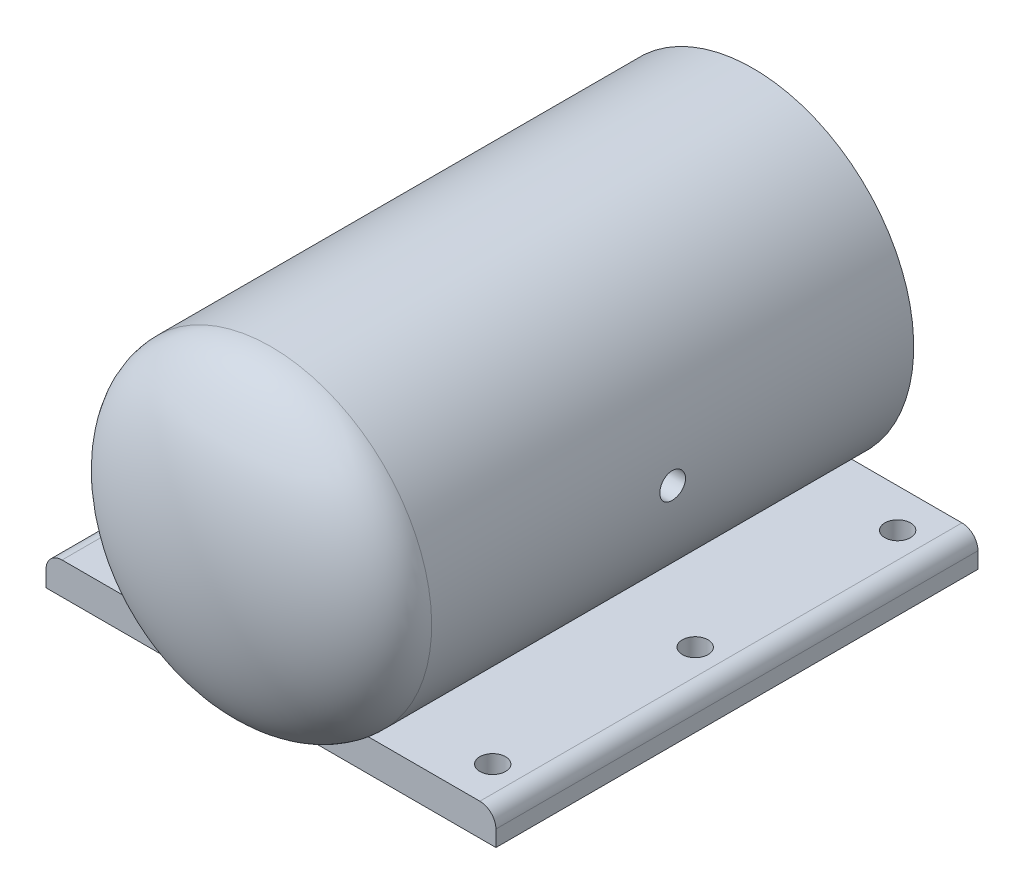
SolidWorks part; units mm, degrees
ref_plane "Front Plane" through (0, 0, 0) normal (0, 0, 1) x (1, 0, 0)
ref_plane "Top Plane" through (0, 0, 0) normal (0, 1, 0) x (1, 0, 0)
ref_plane "Right Plane" through (0, 0, 0) normal (1, 0, 0) x (0, 0, -1)
sketch "Sketch1" plane through (0, 0, 0) normal (0, 0, 1) x (1, 0, 0)
  line L0 (-32.5, -20) -> (-15, -20)
  line L1 (15, -20) -> (32.5, -20)
  line L2 (35, -22.5) -> (35, -25)
  line L3 (35, -25) -> (-35, -25)
  line L4 (-35, -25) -> (-35, -22.5)
  circle A0 centre (0, 0) radius 20
  arc A1 (15, -20) -> (-15, -20) centre (0, 0) ccw
  arc A2 (-35, -22.5) -> (-32.5, -20) centre (-32.5, -22.5) cw
  arc A3 (35, -22.5) -> (32.5, -20) centre (32.5, -22.5) ccw
  point P11 (0, -25)
  point P13 (-35, -20)
  dimension "D1" = 40
  dimension "D2" = 50
  dimension "D6" = 2.5
  dimension "D7" = 2.5
  dimension "D3" = 70
  dimension "D4" = 5
  dimension "D5" = 25
extrude "Boss-Extrude1" add sketch "Sketch1" along normal blind 75
sketch "Sketch2" plane through (0, -20, 0) normal (0, 1, 0) x (1, 0, 0)
  line L0 (-15, 0) -> (-32.5, 0) construction
  line L1 (-32.5, -75) -> (-32.5, 0) construction
  line L2 (-32.5, -37.5) -> (32.5, -37.5) construction
  line L3 (32.5, -75) -> (32.5, 0) construction
  line L4 (0, 0) -> (0, -75) construction
  line L5 (-25, -75) -> (25, -75) construction
  line L6 (28.5, -69) -> (28.5, -6) construction
  line L7 (-28.5, -69) -> (-28.5, -6) construction
  line L8 (-32.5, 0) -> (-35, 0) construction
  circle A0 centre (-28.5, -6) radius 2
  circle A1 centre (-28.5, -6) radius 2
  circle A2 centre (28.5, -6) radius 2
  circle A3 centre (28.5, -69) radius 2
  circle A4 centre (-28.5, -69) radius 2
  circle A5 centre (28.5, -37.5) radius 2
  circle A6 centre (-28.5, -37.5) radius 2
  point P26 (0, 0)
  point P27 (0, 0)
  dimension "D1" = 4
  dimension "D2" = 6
  dimension "D3" = 4
sketch "Sketch3" plane through (0, 0, 0) normal (1, 0, 0) x (0, 0, -1)
  line L0 (-75, -22.5) -> (0, -22.5) construction
  circle A0 centre (-37.5, 0) radius 2
  point P7 (-37.5, -22.5)
  dimension "D1" = 4
extrude "Cut-Extrude2" cut sketch "Sketch3" against normal through all both and the other way through all
sketch "Sketch4" plane through (0, 0, 0) normal (1, 0, 0) x (0, 0, -1)
  line L0 (0, 0) -> (-75, 0) construction
  line L3 (-75, 20) -> (-75, -20) construction
  line L4 (-87.5, 0) -> (-75, 0) construction
  line L5 (-87.5, 0) -> (-84.5, 0)
  line L6 (-75, 25) -> (-75, 22)
  ellipse E0 centre (-75, 0) end of major axis (-75, 25) minor radius 12.5 (-75, 25) -> (-87.5, 0) ccw
  spline S0 degree 1 poles (-75, 22) (-84.5, 0) knots 0 0 1 1 construction
  spline S1 degree 3 poles (-75, 22) (-75.2162, 22) (-75.6369, 21.9589) (-76.5463, 21.6947) (-77.8442, 20.9347) (-79.5545, 19.1351) (-81.1937, 16.4611) (-82.604, 13.0366) (-83.6782, 9.0242) (-84.3483, 4.6186) (-84.5, 1.5286) (-84.5, 0) knots 0 0 0 0 0.098175 0.19635 0.392699 0.589049 0.785398 0.981748 1.178097 1.374447 1.570796 1.570796 1.570796 1.570796
  dimension "D1" = 25
  dimension "D2" = 12.5
  dimension "D3" = 3
revolve "Revolve1" add sketch "Sketch4" angle 360 about L4
extrude "Cut-Extrude3" cut sketch "Sketch2" against normal blind 10 contours A3
extrude "Cut-Extrude4" cut sketch "Sketch2<4>" against normal blind 10 contours A6 | A0 | A4 | A2 | A5 region at (-28.5, -20, 37.5)
sketch "Sketch2<4>" plane through (0, -20, 0) normal (0, 1, 0) x (1, 0, 0) same geometry as "Sketch2"
